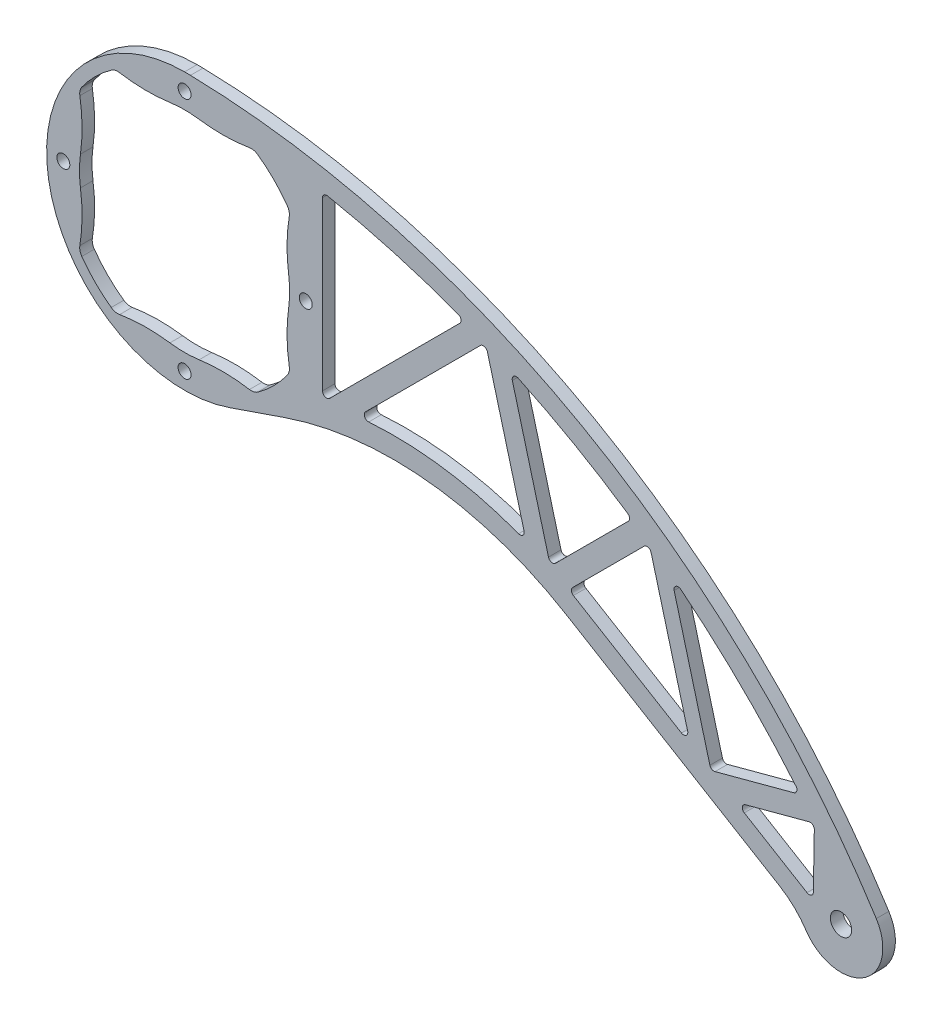
SolidWorks part; units mm, degrees
material "6061 合金"
ref_plane "前视基准面" through (0, 0, 0) normal (0, 0, 1) x (1, 0, 0)
ref_plane "上视基准面" through (0, 0, 0) normal (0, 1, 0) x (1, 0, 0)
ref_plane "右视基准面" through (0, 0, 0) normal (1, 0, 0) x (0, 0, -1)
other "Configuration Table"
sketch "草图2" plane through (0, 0, 0) normal (0, 0, 1) x (1, 0, 0)
  line L1 (10.7304, -31.2067) -> (23.987, -26.6485)
  line L2 (91.2325, -33.7454) -> (142.3676, -64.5004)
  line L3 (0, 0) -> (154.4016, 0) construction
  line L4 (0, 0) -> (157.0595, -65.0562) construction
  line L5 (0, 0) -> (0, -130.9869) construction
  arc A24 (0, 33) -> (10.7304, -31.2067) centre (0, 0) ccw
  arc A25 (148.7262, -70.5839) -> (165.4995, -59.6928) centre (157.0595, -65.0562) ccw
  arc A26 (1.4146, 32.9833) -> (165.4995, -59.6928) centre (-3.3007, -166.9611) cw
  circle A27 centre (-29, 0) radius 1.55
  arc A28 (23.987, -26.6485) -> (91.2325, -33.7454) centre (50, -102.3011) cw
  arc A29 (142.3676, -64.5004) -> (148.7262, -70.5839) centre (132.0595, -81.6393) cw
  arc A30 (1.4146, 32.9833) -> (0, 33) centre (0, -27) ccw
  arc A32 (-24.8547, -15.5614) -> (-24.7074, -3.4705) centre (-64.3186, -9.0345) ccw construction
  arc A33 (-24.8547, -15.5614) -> (-24.4235, -17.4211) centre (-22.3882, -15.9693) ccw construction
  arc A34 (-24.4235, -17.4211) -> (-17.4211, -24.4235) centre (0, 0) ccw construction
  arc A35 (-17.4211, -24.4235) -> (-15.5614, -24.8547) centre (-15.9693, -22.3882) ccw construction
  arc A36 (-3.4705, -24.7074) -> (-15.5614, -24.8547) centre (-9.0345, -64.3186) ccw construction
  arc A37 (-3.4705, -24.7074) -> (3.4705, -24.7074) centre (0, 0) ccw construction
  arc A38 (15.5614, -24.8547) -> (3.4705, -24.7074) centre (9.0345, -64.3186) ccw construction
  arc A39 (15.5614, -24.8547) -> (17.4211, -24.4235) centre (15.9693, -22.3882) ccw construction
  arc A40 (17.4211, -24.4235) -> (24.4235, -17.4211) centre (0, 0) ccw construction
  arc A41 (24.4235, -17.4211) -> (24.8547, -15.5614) centre (22.3882, -15.9693) ccw construction
  arc A42 (24.7074, -3.4705) -> (24.8547, -15.5614) centre (64.3186, -9.0345) ccw construction
  arc A43 (24.7074, -3.4705) -> (24.7074, 3.4705) centre (0, 0) ccw construction
  arc A44 (24.8547, 15.5614) -> (24.7074, 3.4705) centre (64.3186, 9.0345) ccw construction
  arc A45 (24.8547, 15.5614) -> (24.4235, 17.4211) centre (22.3882, 15.9693) ccw construction
  arc A46 (24.4235, 17.4211) -> (17.4211, 24.4235) centre (0, 0) ccw construction
  arc A47 (17.4211, 24.4235) -> (15.5614, 24.8547) centre (15.9693, 22.3882) ccw construction
  arc A48 (3.4705, 24.7074) -> (15.5614, 24.8547) centre (9.0345, 64.3186) ccw construction
  arc A49 (3.4705, 24.7074) -> (-3.4705, 24.7074) centre (0, 0) ccw construction
  arc A50 (-15.5614, 24.8547) -> (-3.4705, 24.7074) centre (-9.0345, 64.3186) ccw construction
  arc A51 (-15.5614, 24.8547) -> (-17.4211, 24.4235) centre (-15.9693, 22.3882) ccw construction
  arc A52 (-17.4211, 24.4235) -> (-24.4235, 17.4211) centre (0, 0) ccw construction
  arc A53 (-24.4235, 17.4211) -> (-24.8547, 15.5614) centre (-22.3882, 15.9693) ccw construction
  arc A54 (-24.7074, 3.4705) -> (-24.8547, 15.5614) centre (-64.3186, 9.0345) ccw construction
  arc A55 (-24.7074, 3.4705) -> (-24.7074, -3.4705) centre (0, 0) ccw construction
  arc A56 (-17.4792, 24.5049) -> (-24.5049, 17.4792) centre (0, 0) ccw
  arc A57 (-24.5049, 17.4792) -> (-24.9533, 15.5451) centre (-22.3882, 15.9693) ccw
  arc A58 (-24.8065, 3.4845) -> (-24.9533, 15.5451) centre (-64.3186, 9.0345) ccw
  arc A59 (-24.8065, 3.4845) -> (-24.8065, -3.4845) centre (0, 0) ccw
  arc A60 (-24.9533, -15.5451) -> (-24.8065, -3.4845) centre (-64.3186, -9.0345) ccw
  arc A61 (-24.9533, -15.5451) -> (-24.5049, -17.4792) centre (-22.3882, -15.9693) ccw
  arc A62 (-24.5049, -17.4792) -> (-17.4792, -24.5049) centre (0, 0) ccw
  arc A63 (-17.4792, -24.5049) -> (-15.5451, -24.9533) centre (-15.9693, -22.3882) ccw
  arc A64 (-3.4845, -24.8065) -> (-15.5451, -24.9533) centre (-9.0345, -64.3186) ccw
  arc A65 (-3.4845, -24.8065) -> (3.4845, -24.8065) centre (0, 0) ccw
  arc A66 (15.5451, -24.9533) -> (3.4845, -24.8065) centre (9.0345, -64.3186) ccw
  arc A67 (15.5451, -24.9533) -> (17.4792, -24.5049) centre (15.9693, -22.3882) ccw
  arc A68 (17.4792, -24.5049) -> (24.5049, -17.4792) centre (0, 0) ccw
  arc A69 (24.5049, -17.4792) -> (24.9533, -15.5451) centre (22.3882, -15.9693) ccw
  arc A70 (24.8065, -3.4845) -> (24.9533, -15.5451) centre (64.3186, -9.0345) ccw
  arc A71 (24.8065, -3.4845) -> (24.8065, 3.4845) centre (0, 0) ccw
  arc A72 (24.9533, 15.5451) -> (24.8065, 3.4845) centre (64.3186, 9.0345) ccw
  arc A73 (24.9533, 15.5451) -> (24.5049, 17.4792) centre (22.3882, 15.9693) ccw
  arc A74 (24.5049, 17.4792) -> (17.4792, 24.5049) centre (0, 0) ccw
  arc A75 (17.4792, 24.5049) -> (15.5451, 24.9533) centre (15.9693, 22.3882) ccw
  arc A76 (3.4845, 24.8065) -> (15.5451, 24.9533) centre (9.0345, 64.3186) ccw
  arc A77 (3.4845, 24.8065) -> (-3.4845, 24.8065) centre (0, 0) ccw
  arc A78 (-15.5451, 24.9533) -> (-3.4845, 24.8065) centre (-9.0345, 64.3186) ccw
  arc A79 (-15.5451, 24.9533) -> (-17.4792, 24.5049) centre (-15.9693, 22.3882) ccw
  circle A80 centre (0, 0) radius 29 construction
  circle A81 centre (0, 29) radius 1.55
  circle A82 centre (0, -29) radius 1.55
  arc A83 (15.5614, -24.8547) -> (3.4705, -24.7074) centre (9.0345, -64.3186) ccw construction
  circle A84 centre (29, 0) radius 1.55
  point P51 (147.0595, -65.0562)
  dimension "D3" = 3.1
  dimension "D5" = 66
  dimension "D6" = 20
  dimension "D7" = 80
  dimension "D9" = 20
  dimension "D10" = 200
  dimension "D11" = 60
  dimension "D13" = 50
  dimension "D1" = 170
  dimension "D2" = 130
  dimension "D4" = 29
  dimension "D8" = 22.5
  dimension "D12" = 0.1
  dimension "D14" = 25
extrude "凸台-拉伸1" add sketch "草图2" along normal blind 3
sketch "草图7" plane through (0, 0, 3) normal (0, 0, 1) x (1, 0, 0)
  circle A0 centre (157.0595, -65.0562) radius 2.55
  arc A1 (148.7262, -70.5839) -> (165.4995, -59.6928) centre (157.0595, -65.0562) ccw construction
  dimension "D1" = 5.1
extrude "切除-拉伸2" cut sketch "草图7" against normal blind 5
sketch "草图9" plane through (0, 0, 3) normal (0, 0, 1) x (1, 0, 0)
  line L0 (93.8095, -29.4607) -> (77.7146, -19.7805) construction
  line L2 (10.7304, -31.2067) -> (23.987, -26.6485)
  line L3 (91.2325, -33.7454) -> (142.3676, -64.5004)
  line L6 (33, 23.4192) -> (33, -16.6042)
  line L7 (34.7071, -17.3113) -> (65.8687, 13.8502)
  line L8 (70.7773, 11.6878) -> (43.2854, -15.8041)
  line L9 (72.4503, 11.2395) -> (81.2349, -21.5452)
  line L10 (78.4208, 8.276) -> (87.0701, -24.0039)
  line L11 (88.7431, -24.4522) -> (106.1707, -7.0247)
  line L12 (14.8183, -31.2257) -> (-22.149, -67.7394) construction
  line L13 (-23.9266, -76.5229) -> (-33.3984, -85.8785) construction
  line L14 (109.9456, -10.3208) -> (92.8385, -27.4279)
  line L15 (93.0302, -28.992) -> (118.8884, -44.5443)
  line L16 (93.8095, -29.4607) -> (144.9447, -60.2157) construction
  line L17 (91.2325, -33.7454) -> (142.3676, -64.5004) construction
  line L18 (111.6187, -10.7691) -> (120.3697, -43.4285)
  line L29 (117.1346, -15.8999) -> (125.6886, -47.8239)
  line L30 (93.8095, -29.4607) -> (144.9447, -60.2157)
  line L31 (93.8095, -29.4607) -> (144.9447, -60.2157) construction
  line L32 (126.9133, -48.531) -> (145.7798, -43.4758)
  line L33 (149.4125, -47.6788) -> (134.1757, -51.7615)
  line L34 (150.6712, -48.6626) -> (150.4368, -61.7685)
  line L35 (133.9191, -53.5844) -> (148.9215, -62.6075)
  arc A1 (79.917, -22.74) -> (44.0624, -17.5087) centre (50, -102.3011) ccw
  arc A7 (148.7262, -70.5839) -> (142.3676, -64.5004) centre (132.0595, -81.6393) ccw
  arc A8 (148.7262, -70.5839) -> (165.4995, -59.6928) centre (157.0595, -65.0562) ccw
  arc A9 (165.4995, -59.6928) -> (1.4146, 32.9833) centre (-3.3007, -166.9611) ccw
  arc A10 (1.4146, 32.9833) -> (0, 33) centre (0, -27) ccw
  arc A11 (117.1346, -15.8999) -> (118.7263, -14.861) centre (118.1005, -15.641) cw
  arc A12 (0, 33) -> (10.7304, -31.2067) centre (0, 0) ccw
  arc A13 (91.2325, -33.7454) -> (23.987, -26.6485) centre (50, -102.3011) ccw
  arc A15 (148.7262, -70.5839) -> (156.4086, -55.0774) centre (157.0595, -65.0562) ccw construction
  arc A21 (161.2795, -62.3745) -> (1.2967, 27.9847) centre (-3.3007, -166.9611) ccw construction
  arc A22 (93.8095, -29.4607) -> (-33.3984, -85.8785) centre (50, -102.3011) ccw construction
  arc A23 (65.5144, 15.493) -> (34.1923, 24.4006) centre (-3.3007, -166.9611) ccw
  arc A24 (106.0242, -5.4895) -> (79.8129, 9.4394) centre (-3.3007, -166.9611) ccw
  arc A27 (152.8929, -67.82) -> (144.9447, -60.2157) centre (132.0595, -81.6393) ccw construction
  arc A28 (165.4995, -59.6928) -> (1.4146, 32.9833) centre (-3.3007, -166.9611) ccw construction
  arc A29 (1.2967, 27.9847) -> (-23.9266, -76.5229) centre (0, -27) ccw construction
  arc A30 (1.4146, 32.9833) -> (15.1955, 31.0439) centre (0, -27) ccw construction
  circle A31 centre (3.5031, 49.1035) radius 21.5142 construction
  arc A32 (-23.9266, -76.5229) -> (-23.9266, -76.5229) centre (-23.9266, -76.5229) ccw construction
  arc A33 (-23.9266, -76.5229) -> (-23.9266, -76.5229) centre (-23.9266, -76.5229) cw construction
  arc A34 (15.1955, 31.0439) -> (14.8183, -31.2257) centre (0, 0) ccw construction
  arc A35 (91.2325, -33.7454) -> (-22.149, -67.7394) centre (50, -102.3011) ccw construction
  arc A36 (148.7262, -70.5839) -> (142.3676, -64.5004) centre (132.0595, -81.6393) ccw construction
  arc A37 (148.7262, -70.5839) -> (165.4995, -59.6928) centre (157.0595, -65.0562) ccw construction
  arc A38 (152.8929, -67.82) -> (161.2795, -62.3745) centre (157.0595, -65.0562) ccw construction
  arc A42 (92.8385, -27.4279) -> (93.0302, -28.992) centre (93.5456, -28.135) ccw
  arc A43 (109.9456, -10.3208) -> (111.6187, -10.7691) centre (110.6527, -11.0279) cw
  arc A44 (106.1707, -7.0247) -> (106.0242, -5.4895) centre (105.4636, -6.3176) ccw
  arc A45 (78.4208, 8.276) -> (79.8129, 9.4394) centre (79.3867, 8.5348) cw
  arc A46 (87.0701, -24.0039) -> (88.7431, -24.4522) centre (88.036, -23.7451) ccw
  arc A47 (43.2854, -15.8041) -> (44.0624, -17.5087) centre (43.9926, -16.5112) ccw
  arc A48 (70.7773, 11.6878) -> (72.4503, 11.2395) centre (71.4844, 10.9806) cw
  arc A49 (65.8687, 13.8502) -> (65.5144, 15.493) centre (65.1615, 14.5573) ccw
  arc A50 (33, -16.6042) -> (34.7071, -17.3113) centre (34, -16.6042) ccw
  arc A51 (33, 23.4192) -> (34.1923, 24.4006) centre (34, 23.4192) cw
  arc A52 (81.2349, -21.5452) -> (79.917, -22.74) centre (80.269, -21.804) cw
  arc A53 (120.3697, -43.4285) -> (118.8884, -44.5443) centre (119.4038, -43.6873) cw
  arc A58 (145.7798, -43.4758) -> (146.2881, -41.8684) centre (145.521, -42.5099) ccw
  arc A60 (125.6886, -47.8239) -> (126.9133, -48.531) centre (126.6545, -47.5651) ccw
  arc A61 (134.1757, -51.7615) -> (133.9191, -53.5844) centre (134.4345, -52.7274) ccw
  arc A62 (149.4125, -47.6788) -> (150.6712, -48.6626) centre (149.6713, -48.6447) cw
  arc A63 (161.2795, -62.3745) -> (1.2967, 27.9847) centre (-3.3007, -166.9611) ccw
  arc A64 (161.2795, -62.3745) -> (156.4086, -55.0774) centre (-3.3007, -166.9611) ccw construction
  arc A65 (146.2881, -41.8684) -> (118.7263, -14.861) centre (-3.3007, -166.9611) ccw
  arc A66 (152.8929, -67.82) -> (144.9447, -60.2157) centre (132.0595, -81.6393) ccw
  arc A67 (152.8929, -67.82) -> (144.9447, -60.2157) centre (132.0595, -81.6393) ccw construction
  arc A68 (150.4368, -61.7685) -> (148.9215, -62.6075) centre (149.4369, -61.7506) cw
  circle A69 centre (29, 0) radius 1.55 construction
  point P54 (119.853, -45.1244)
  point P60 (91.9338, -28.3326)
  point P63 (111.1704, -9.096)
  point P66 (107.0242, -6.1711)
  point P71 (87.5184, -25.6769)
  point P76 (72.002, 12.9125)
  point P79 (66.9597, 14.9413)
  point P82 (33, -19.0185)
  point P88 (147.2865, -43.0721)
  point P96 (125.9474, -48.7899)
  point P99 (131.9014, -52.3709)
  point P103 (150.6949, -47.3352)
  point P106 (150.4058, -63.5002)
  dimension "D12" = 5
  dimension "D14" = 90
  dimension "D15" = 1
  dimension "D16" = 1
  dimension "D17" = 5
  dimension "D18" = 5
  dimension "D13" = 4
  dimension "D19" = 1
  dimension "D3" = 4
  dimension "D4" = 45
  dimension "D5" = 5
  dimension "D6" = 60
  dimension "D7" = 5
  dimension "D8" = 60
  dimension "D9" = 5
  dimension "D10" = 60
  dimension "D11" = 5
  dimension "D20" = 60
  dimension "D1" = 0
  dimension "D2" = 5
extrude "切除-拉伸4" cut sketch "草图9" against normal through all
sketch "草图10" plane through (0, 0, 3) normal (0, 0, 1) x (1, 0, 0)
  arc A48 (-3.4984, -24.9055) -> (-15.5288, -25.052) centre (-9.0345, -64.3186) ccw
  arc A49 (-17.5372, -24.5863) -> (-15.5288, -25.052) centre (-15.9693, -22.3882) ccw
  arc A50 (-24.5863, -17.5372) -> (-17.5372, -24.5863) centre (0, 0) ccw
  arc A51 (-25.052, -15.5288) -> (-24.5863, -17.5372) centre (-22.3882, -15.9693) ccw
  arc A52 (-25.052, -15.5288) -> (-24.9055, -3.4984) centre (-64.3186, -9.0345) ccw
  arc A53 (-24.9055, 3.4984) -> (-24.9055, -3.4984) centre (0, 0) ccw
  arc A54 (-24.9055, 3.4984) -> (-25.052, 15.5288) centre (-64.3186, 9.0345) ccw
  arc A55 (-24.5863, 17.5372) -> (-25.052, 15.5288) centre (-22.3882, 15.9693) ccw
  arc A56 (-17.5372, 24.5863) -> (-24.5863, 17.5372) centre (0, 0) ccw
  arc A57 (-15.5288, 25.052) -> (-17.5372, 24.5863) centre (-15.9693, 22.3882) ccw
  arc A58 (-15.5288, 25.052) -> (-3.4984, 24.9055) centre (-9.0345, 64.3186) ccw
  arc A59 (3.4984, 24.9055) -> (-3.4984, 24.9055) centre (0, 0) ccw
  arc A60 (3.4984, 24.9055) -> (15.5288, 25.052) centre (9.0345, 64.3186) ccw
  arc A61 (17.5372, 24.5863) -> (15.5288, 25.052) centre (15.9693, 22.3882) ccw
  arc A62 (24.5863, 17.5372) -> (17.5372, 24.5863) centre (0, 0) ccw
  arc A63 (25.052, 15.5288) -> (24.5863, 17.5372) centre (22.3882, 15.9693) ccw
  arc A64 (25.052, 15.5288) -> (24.9055, 3.4984) centre (64.3186, 9.0345) ccw
  arc A65 (24.9055, -3.4984) -> (24.9055, 3.4984) centre (0, 0) ccw
  arc A66 (24.9055, -3.4984) -> (25.052, -15.5288) centre (64.3186, -9.0345) ccw
  arc A67 (24.5863, -17.5372) -> (25.052, -15.5288) centre (22.3882, -15.9693) ccw
  arc A68 (17.5372, -24.5863) -> (24.5863, -17.5372) centre (0, 0) ccw
  arc A69 (15.5288, -25.052) -> (17.5372, -24.5863) centre (15.9693, -22.3882) ccw
  arc A70 (15.5288, -25.052) -> (3.4984, -24.9055) centre (9.0345, -64.3186) ccw
  arc A71 (-3.4984, -24.9055) -> (3.4984, -24.9055) centre (0, 0) ccw
  arc A72 (-3.4984, -24.9055) -> (-15.5288, -25.052) centre (-9.0345, -64.3186) ccw
  arc A73 (-17.5372, -24.5863) -> (-15.5288, -25.052) centre (-15.9693, -22.3882) ccw
  arc A74 (-24.5863, -17.5372) -> (-17.5372, -24.5863) centre (0, 0) ccw
  arc A75 (-25.052, -15.5288) -> (-24.5863, -17.5372) centre (-22.3882, -15.9693) ccw
  arc A76 (-25.052, -15.5288) -> (-24.9055, -3.4984) centre (-64.3186, -9.0345) ccw
  arc A77 (-24.9055, 3.4984) -> (-24.9055, -3.4984) centre (0, 0) ccw
  arc A78 (-24.9055, 3.4984) -> (-25.052, 15.5288) centre (-64.3186, 9.0345) ccw
  arc A79 (-24.5863, 17.5372) -> (-25.052, 15.5288) centre (-22.3882, 15.9693) ccw
  arc A80 (-17.5372, 24.5863) -> (-24.5863, 17.5372) centre (0, 0) ccw
  arc A81 (-15.5288, 25.052) -> (-17.5372, 24.5863) centre (-15.9693, 22.3882) ccw
  arc A82 (-15.5288, 25.052) -> (-3.4984, 24.9055) centre (-9.0345, 64.3186) ccw
  arc A83 (3.4984, 24.9055) -> (-3.4984, 24.9055) centre (0, 0) ccw
  arc A84 (3.4984, 24.9055) -> (15.5288, 25.052) centre (9.0345, 64.3186) ccw
  arc A85 (17.5372, 24.5863) -> (15.5288, 25.052) centre (15.9693, 22.3882) ccw
  arc A86 (24.5863, 17.5372) -> (17.5372, 24.5863) centre (0, 0) ccw
  arc A87 (25.052, 15.5288) -> (24.5863, 17.5372) centre (22.3882, 15.9693) ccw
  arc A88 (25.052, 15.5288) -> (24.9055, 3.4984) centre (64.3186, 9.0345) ccw
  arc A89 (24.9055, -3.4984) -> (24.9055, 3.4984) centre (0, 0) ccw
  arc A90 (24.9055, -3.4984) -> (25.052, -15.5288) centre (64.3186, -9.0345) ccw
  arc A91 (24.5863, -17.5372) -> (25.052, -15.5288) centre (22.3882, -15.9693) ccw
  arc A92 (17.5372, -24.5863) -> (24.5863, -17.5372) centre (0, 0) ccw
  arc A93 (15.5288, -25.052) -> (17.5372, -24.5863) centre (15.9693, -22.3882) ccw
  arc A94 (15.5288, -25.052) -> (3.4984, -24.9055) centre (9.0345, -64.3186) ccw
  arc A95 (-3.4984, -24.9055) -> (3.4984, -24.9055) centre (0, 0) ccw
  dimension "D1" = 0.1
extrude "切除-拉伸5" cut sketch "草图10" against normal through all
